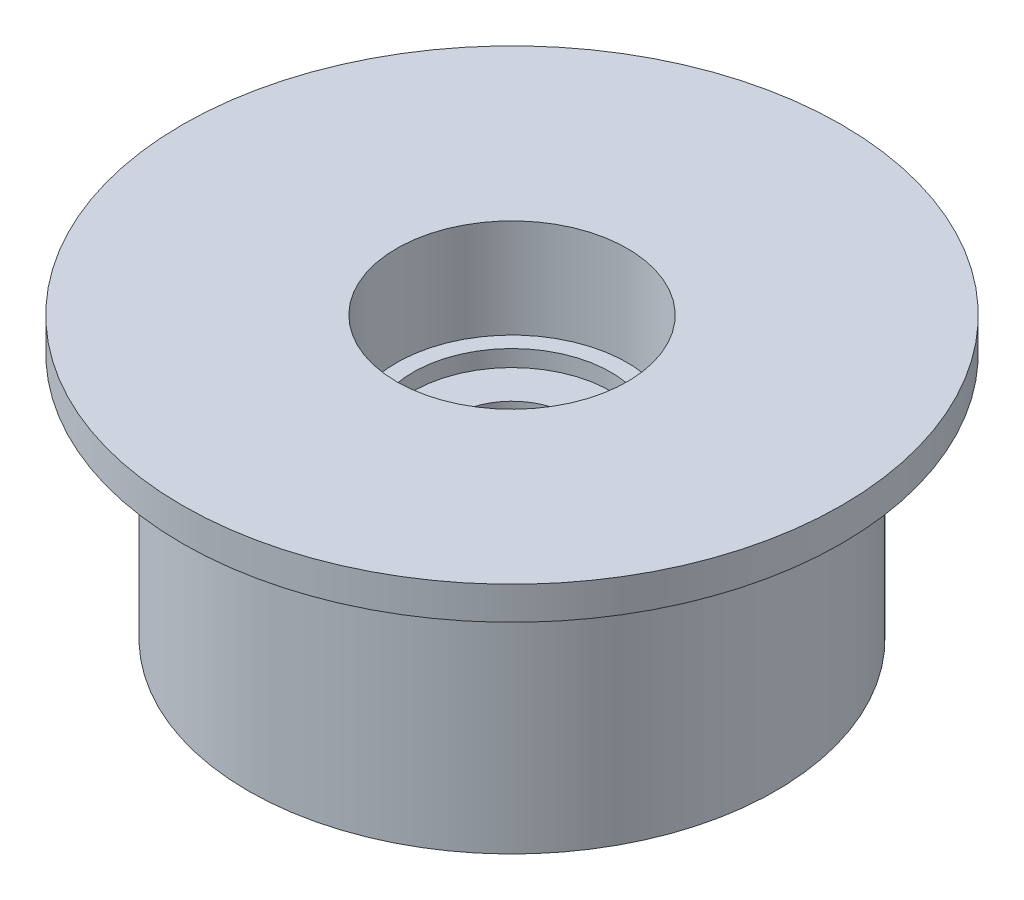
SolidWorks part; units mm, degrees
ref_plane "Front Plane" through (0, 0, 0) normal (0, 0, 1) x (1, 0, 0)
ref_plane "Top Plane" through (0, 0, 0) normal (0, 1, 0) x (1, 0, 0)
ref_plane "Right Plane" through (0, 0, 0) normal (1, 0, 0) x (0, 0, -1)
sketch "Sketch1" plane through (0, 0, 0) normal (0, 0, 1) x (1, 0, 0)
  line L0 (1.75, 0) -> (8, 0)
  line L1 (3.5, 8.5) -> (10, 8.5)
  line L2 (10, 8.5) -> (10, 7.5)
  line L3 (10, 7.5) -> (8, 7.5)
  line L4 (8, 7.5) -> (8, 0)
  line L7 (3.5, 8.5) -> (3.5, 5.5)
  line L8 (3.5, 5.5) -> (3, 5.5)
  line L9 (3, 5.5) -> (3, 5)
  line L10 (3, 5) -> (1.75, 5)
  line L11 (1.75, 5) -> (1.75, 0)
  point P0 (1.75, 2.5)
  point P14 (-3.5555, 29.6487)
  dimension "D2" = 1
  dimension "D3" = 1.75
  dimension "D4" = 0.5
  dimension "D5" = 0.5
  dimension "D6" = 2
  dimension "D7" = 3
  dimension "D9" = 5
  dimension "D12" = 8
  dimension "D13" = 3.5
ref_axis "Axis1" through (0, 37.275, 0) along (0, -1, 0)
revolve "Revolve1" add sketch "Sketch1" angle 360 about axis through (0, 37.275, 0) along (0, -1, 0)
